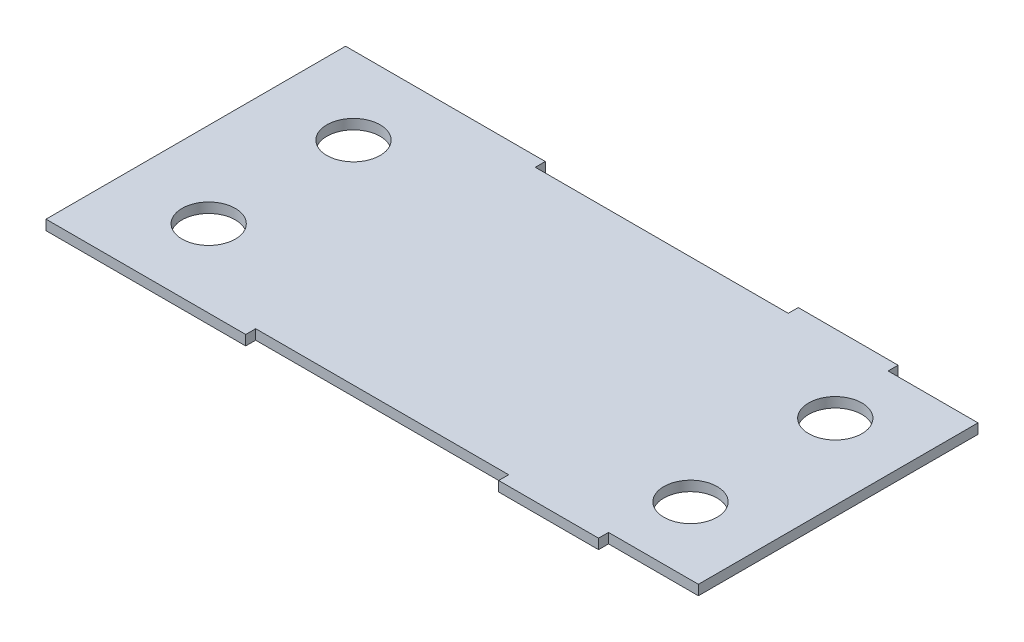
SolidWorks part; units mm, degrees
ref_plane "Front Plane" through (0, 0, 0) normal (0, 0, 1) x (1, 0, 0)
ref_plane "Top Plane" through (0, 0, 0) normal (0, 1, 0) x (1, 0, 0)
ref_plane "Right Plane" through (0, 0, 0) normal (1, 0, 0) x (0, 0, -1)
sketch "Sketch1" plane through (0, 0, 0) normal (0, 1, 0) x (1, 0, 0)
  line L0 (38, 45) -> (38, 42)
  line L1 (68, -42) -> (95, -42)
  line L2 (-98, -45) -> (-98, 45)
  line L3 (95, 45) -> (-98, 45)
  line L4 (68, 42) -> (95, 42)
  line L5 (95, -45) -> (-98, -45)
  line L7 (38, 42) -> (-38, 42)
  line L8 (-38, 42) -> (-38, 45)
  line L10 (68, 42) -> (68, 45)
  line L11 (95, -45) -> (95, 45)
  line L15 (-38, -45) -> (-38, -42)
  line L16 (-38, -42) -> (38, -42)
  line L17 (38, -42) -> (38, -45)
  line L18 (38, -45) -> (68, -45)
  line L19 (68, -45) -> (68, -42)
  circle A0 centre (72.375, -21.75) radius 8
  circle A1 centre (72.375, 21.75) radius 8
  circle A2 centre (-72.375, 21.75) radius 8
  circle A3 centre (-72.375, -21.75) radius 8
  point P0 (0, 0)
  dimension "D7" = 16
  dimension "D10" = 16
  dimension "D18" = 16
  dimension "D19" = 16
  dimension "D3" = 27
  dimension "D4" = 30
  dimension "D5" = 60
  dimension "D6" = 90
  dimension "D9" = 30
  dimension "D11" = 3
  dimension "D12" = 3
  dimension "D13" = 3
  dimension "D14" = 22.625
  dimension "D15" = 22.625
  dimension "D22" = 25.625
  dimension "D23" = 25.625
  dimension "D24" = 76
  dimension "D25" = 60
  dimension "D26" = 76
  dimension "D27" = 193
  dimension "D28" = 27
extrude "Boss-Extrude1" add sketch "Sketch1" along normal blind 3 contours L19 L11 L10 L0 L7 L8 L2 L15 L16 L17 A3 A2 A1 A0 region at (-2.4617, 0, 0)
